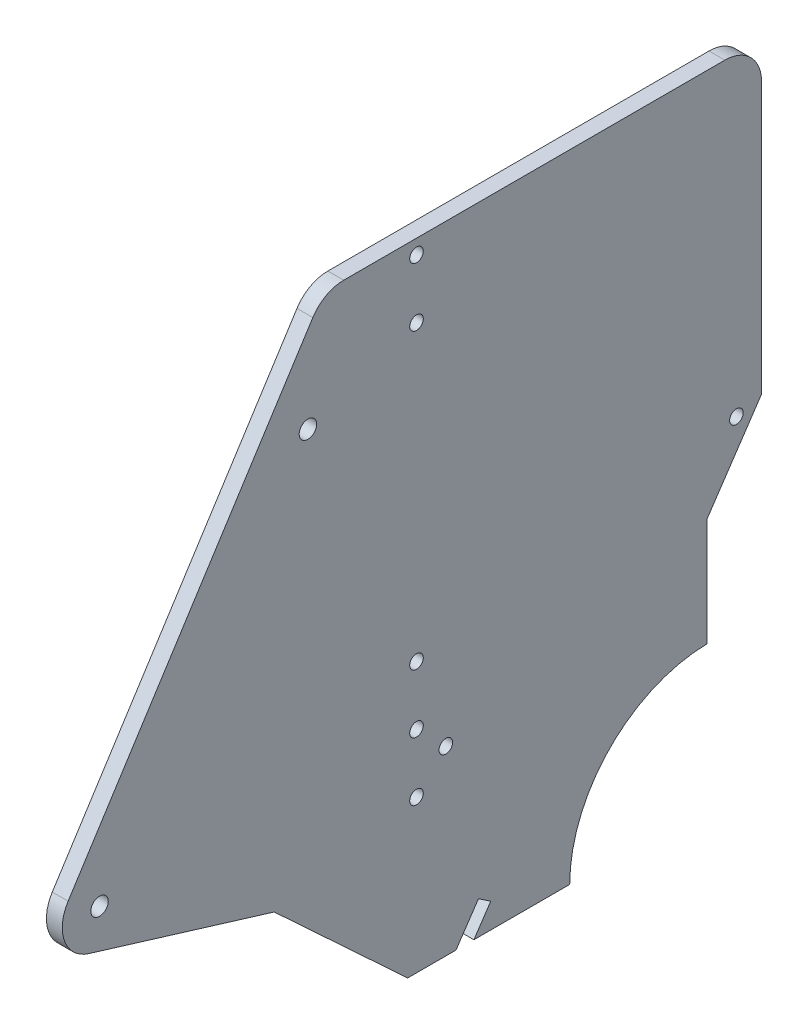
SolidWorks part; units mm, degrees
material "Acrylic (Medium-high impact)"
ref_plane "Front" through (0, 0, 0) normal (0, 0, 1) x (1, 0, 0)
ref_plane "Top" through (0, 0, 0) normal (0, 1, 0) x (1, 0, 0)
ref_plane "Right" through (0, 0, 0) normal (1, 0, 0) x (0, 0, -1)
ref_axis "side-side" through (80.9, 0, 0) along (-1, 0, 0)
ref_axis "up-down" through (0, 50, 0) along (0, -1, 0)
ref_axis "front-back" through (0, 0, -80.9) along (0, 0, 1)
sketch "Sketch1" plane through (0, 0, 0) normal (1, 0, 0) x (0, 0, -1)
  line L1 (-114.2854, 109.5191) -> (-221.6238, -49.6166)
  line L3 (-114.2854, 109.5191) -> (-110.9692, 107.2824)
  line L5 (-218.3076, -51.8533) -> (-110.9692, 107.2824)
  line L10 (-277.2593, 32) -> (-277.2593, 30)
  line L11 (133.7407, 32) -> (-277.2593, 32)
  line L12 (133.7407, 30) -> (133.7407, 32)
  line L13 (-277.2593, 30) -> (133.7407, 30)
  line L18 (-277.2593, 2) -> (-277.2593, 0)
  line L19 (133.7407, 2) -> (-277.2593, 2)
  line L20 (133.7407, 0) -> (133.7407, 2)
  line L21 (-277.2593, 0) -> (133.7407, 0)
  line L23 (-119.7593, 64) -> (-117.7593, 64)
  line L25 (-87.7593, 64) -> (-89.7593, 64)
  line L38 (-117.2593, 32) -> (-90.2593, 32)
  line L39 (-87.7593, 34.5) -> (-87.7593, 61.5)
  line L40 (-87.7593, 61.5) -> (-89.7593, 61.5)
  line L41 (-89.7593, 61.5) -> (-89.7593, 34)
  line L42 (-89.7593, 34) -> (-117.7593, 34)
  line L43 (-117.7593, 34) -> (-117.7593, 61.5)
  line L44 (-117.7593, 61.5) -> (-119.7593, 61.5)
  line L45 (-119.7593, 61.5) -> (-119.7593, 34.5)
  circle A1 centre (-286.3713, 57.4304) radius 2.3813
  circle A3 centre (-229.5573, 141.6606) radius 2.3813
  circle A5 centre (-141.6718, 148.4823) radius 47.625
  arc A8 (-90.2593, 32) -> (-87.7593, 34.5) centre (-90.2593, 34.5) ccw
  arc A9 (-119.7593, 34.5) -> (-117.2593, 32) centre (-117.2593, 34.5) ccw
sketch "Sketch2" plane through (0, 0, 0) normal (1, 0, 0) x (0, 0, -1)
  line L0 (-115.8892, 171.954) -> (-219.7991, 171.954)
  line L1 (133.7407, 32) -> (-277.2593, 32) construction
  line L2 (-228.2267, 167.3369) -> (-294.9337, 62.8994)
  line L3 (-289.341, 47.7141) -> (-238.7597, 32.254)
  line L4 (-277.2593, 0) -> (133.7407, 0) construction
  line L5 (-238.7597, 32.254) -> (-105.8892, 32.254) construction
  line L6 (-277.2593, 30) -> (133.7407, 30) construction
  line L7 (133.7407, 2) -> (-277.2593, 2) construction
  line L8 (-277.2593, 32) -> (-277.2593, 30) construction
  line L9 (-105.8892, 88.0777) -> (-105.8892, 161.954)
  line L10 (-158.1882, 29.746) -> (-277.2593, 29.746) construction
  line L11 (-158.1882, 29.746) -> (-158.1882, 2.254) construction
  line L12 (-158.1882, 2.254) -> (-277.2593, 2.254) construction
  line L13 (-277.2593, 29.746) -> (-277.2593, 2.254) construction
  line L14 (-140.642, 6.368) -> (-288.194, 51.467) construction
  line L15 (-218.3076, -51.8533) -> (-110.9692, 107.2824) construction
  line L16 (-238.7597, 32.254) -> (-202.3597, -1.524)
  line L17 (-202.3597, -1.524) -> (-189.1849, -1.524)
  line L19 (-120.7593, 66.032) -> (-105.8892, 66.032) construction
  line L20 (-120.7593, 34.5) -> (-120.7593, 61.5)
  line L21 (-120.7593, 36.576) -> (-120.7593, 66.032)
  line L22 (-119.7593, 64) -> (-117.7593, 64) construction
  line L23 (-183.0681, 7.5446) -> (-189.1849, -1.524)
  line L24 (-183.0681, 7.5446) -> (-179.7202, 5.2864)
  line L25 (-120.7593, 66.032) -> (-105.8892, 88.0777)
  line L26 (-126.9137, 79.4984) -> (-111.8155, 101.8824) construction
  line L27 (-184.3139, -1.524) -> (-158.1882, -1.524)
  line L28 (-179.7202, 5.2864) -> (-184.3139, -1.524)
  line L29 (-114.2854, 109.5191) -> (-221.6238, -49.6166) construction
  line L31 (-179.6019, 4.9615) -> (-183.1817, 7.3761) construction
  arc A0 (-294.9337, 62.8994) -> (-289.341, 47.7141) centre (-286.3713, 57.4304) ccw
  circle A1 centre (-286.3713, 57.4304) radius 2.3813 construction
  circle A2 centre (-286.3713, 57.4304) radius 2.3813
  circle A3 centre (-229.5573, 141.6606) radius 2.3813 construction
  circle A4 centre (-229.5573, 141.6606) radius 2.3813
  arc A5 (-120.7593, 36.576) -> (-158.1882, -1.524) centre (-120.0821, -1.524) ccw
  arc A6 (-105.8892, 161.954) -> (-115.8892, 171.954) centre (-115.8892, 161.954) ccw
  arc A7 (-228.2267, 167.3369) -> (-219.7991, 171.954) centre (-219.7991, 161.954) cw
  circle A8 centre (-112.7323, 86.2169) radius 1.85 construction
  circle A9 centre (-112.7323, 86.2169) radius 1.85
  circle A10 centre (-199.956, 72) radius 1.85 construction
  circle A11 centre (-199.956, 152) radius 1.85 construction
  circle A12 centre (-199.956, 168) radius 1.85 construction
  circle A13 centre (-199.956, 72) radius 1.85
  circle A14 centre (-199.956, 152) radius 1.85
  circle A15 centre (-199.956, 168) radius 1.85
  circle A16 centre (-199.956, 40) radius 1.85 construction
  circle A17 centre (-191.956, 48) radius 1.85 construction
  circle A18 centre (-199.956, 56) radius 1.85 construction
  circle A19 centre (-199.956, 40) radius 1.85
  circle A20 centre (-191.956, 48) radius 1.85
  circle A21 centre (-199.956, 56) radius 1.85
  point P28 (-163.2682, 29.746)
  dimension "D1" = 10.16
  dimension "D14" = 10
  dimension "D2" = 139.7
  dimension "D3" = 5.08
  dimension "D4" = 0.254
  dimension "D5" = 0.254
  dimension "D6" = 0.254
  dimension "D7" = 5.08
  dimension "D8" = 12.7
  dimension "D9" = 36.4
  dimension "D10" = 1.524
  dimension "D12" = 2.032
  dimension "D13" = 38.1
  dimension "D16" = 4.0383
  dimension "D17" = 0.2032
  dimension "D11" = 1
extrude "Boss-Extrude1" add sketch "Sketch2" along normal blind 4.318
